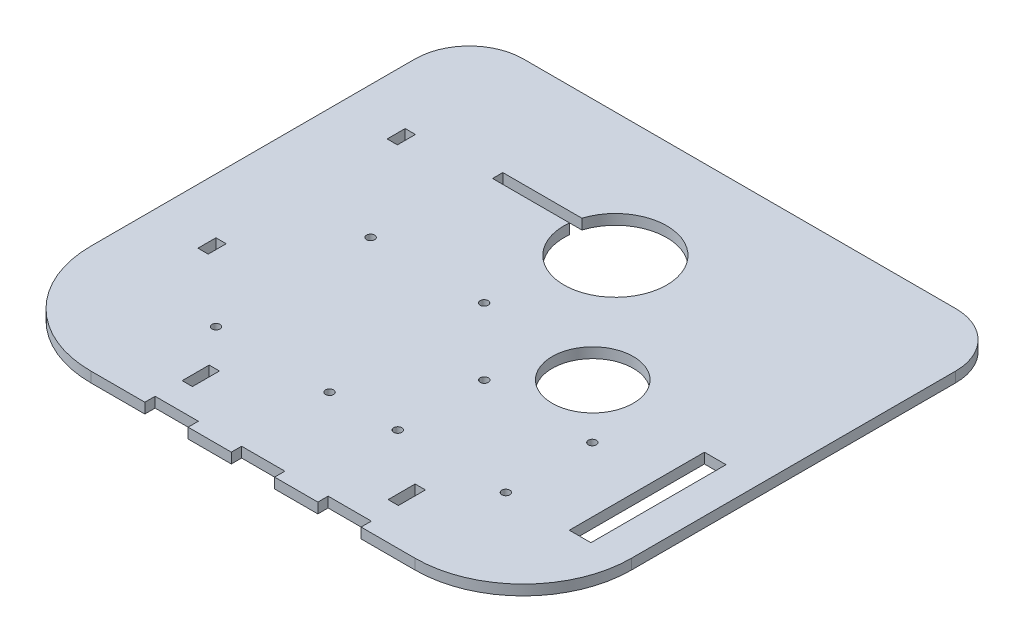
SolidWorks part; units mm, degrees
ref_plane "Front Plane" through (0, 0, 0) normal (0, 0, 1) x (1, 0, 0)
ref_plane "Top Plane" through (0, 0, 0) normal (0, 1, 0) x (1, 0, 0)
ref_plane "Right Plane" through (0, 0, 0) normal (1, 0, 0) x (0, 0, -1)
sketch "Sketch1" plane through (0, 0, 0) normal (0, 1, 0) x (1, 0, 0)
  line L1 (-127, 114.3) -> (127, 114.3)
  line L2 (-127, 114.3) -> (-127, -114.3)
  line L3 (-127, -114.3) -> (127, -114.3)
  line L4 (127, 114.3) -> (127, -114.3)
  line L5 (-127, 114.3) -> (127, -114.3) construction
  line L6 (-127, -114.3) -> (127, 114.3) construction
  point P0 (0, 0)
  dimension "D1" = 254
  dimension "D2" = 228.6
extrude "Boss-Extrude1" add sketch "Sketch1" along normal blind 4.826
sketch "Sketch4" plane through (0, 4.826, 0) normal (0, 1, 0) x (1, 0, 0)
  line L0 (0, -114.3) -> (0, 114.3) construction
  line L1 (-127, -114.3) -> (127, -114.3) construction
  line L2 (127, 114.3) -> (-127, 114.3) construction
  line L3 (-127, 88.9) -> (-101.6, 88.9) construction
  line L4 (-127, 114.3) -> (-127, -114.3) construction
  line L5 (-101.6, 88.9) -> (-101.6, 114.3) construction
  line L6 (-127, 88.9) -> (-127, 114.3)
  line L7 (-127, 114.3) -> (-101.6, 114.3)
  line L8 (127, 88.9) -> (127, 114.3)
  line L9 (127, 114.3) -> (101.6, 114.3)
  arc A0 (-127, 88.9) -> (-101.6, 114.3) centre (-101.6, 88.9) cw
  arc A1 (127, 88.9) -> (101.6, 114.3) centre (101.6, 88.9) ccw
  dimension "D1" = 25.4
  dimension "D2" = 25.4
extrude "Cut-Extrude3" cut sketch "Sketch4" against normal blind 4.826
sketch "Sketch19" plane through (0, 4.826, 0) normal (0, 1, 0) x (1, 0, 0)
  line L0 (-101, -39.1583) -> (-101, -30.6917) construction
  line L1 (-101, -39.1583) -> (-96.174, -39.1583) construction
  line L2 (-96.174, -39.1583) -> (-96.174, -30.6917) construction
  line L3 (-101, -30.6917) -> (-96.174, -30.6917) construction
  line L4 (-101, 49.7417) -> (-101, 58.2083) construction
  line L5 (-101, 49.7417) -> (-96.174, 49.7417) construction
  line L6 (-96.174, 49.7417) -> (-96.174, 58.2083) construction
  line L7 (-101, 58.2083) -> (-96.174, 58.2083) construction
  line L8 (-101, -39.1583) -> (-101, -30.6917)
  line L9 (-101, -39.1583) -> (-96.174, -39.1583)
  line L10 (-96.174, -39.1583) -> (-96.174, -30.6917)
  line L11 (-101, -30.6917) -> (-96.174, -30.6917)
  line L12 (-101, 49.7417) -> (-101, 58.2083)
  line L13 (-101, 49.7417) -> (-96.174, 49.7417)
  line L14 (-96.174, 49.7417) -> (-96.174, 58.2083)
  line L15 (-101, 58.2083) -> (-96.174, 58.2083)
extrude "Cut-Extrude16" cut sketch "Sketch19" against normal through all
fillet "Fillet11" radius 50.8 2 edges at (-127, 2.413, 114.3) (127, 2.413, 114.3)
sketch "Sketch20" plane through (0, 0, 0) normal (0, -1, 0) x (1, 0, 0)
  line L1 (101, 66.675) -> (111.16, 66.675)
  line L2 (101, 66.675) -> (101, 3.175)
  line L3 (101, 3.175) -> (111.16, 3.175)
  line L4 (111.16, 66.675) -> (111.16, 3.175)
  dimension "D1" = 10.16
extrude "Cut-Extrude17" cut sketch "Sketch20" against normal through all
sketch "Sketch23" plane through (0, 4.826, 0) normal (0, 1, 0) x (1, 0, 0)
  circle A0 centre (70.7411, -25.5764) radius 1.905 construction
  circle A1 centre (70.7411, -66.2164) radius 1.905 construction
  circle A2 centre (19.9411, -25.5764) radius 1.905 construction
  circle A3 centre (19.9411, -66.2164) radius 1.905 construction
  circle A4 centre (-11.4804, 5.7926) radius 1.905 construction
  circle A5 centre (-64.8204, 5.7926) radius 1.905 construction
  circle A6 centre (-64.8204, -66.8514) radius 1.905 construction
  circle A7 centre (-11.4804, -66.8514) radius 1.905 construction
  circle A8 centre (70.7411, -25.5764) radius 1.905
  circle A9 centre (70.7411, -66.2164) radius 1.905
  circle A10 centre (19.9411, -25.5764) radius 1.905
  circle A11 centre (19.9411, -66.2164) radius 1.905
  circle A12 centre (-11.4804, 5.7926) radius 1.905
  circle A13 centre (-64.8204, 5.7926) radius 1.905
  circle A14 centre (-64.8204, -66.8514) radius 1.905
  circle A15 centre (-11.4804, -66.8514) radius 1.905
extrude "Cut-Extrude18" cut sketch "Sketch23" against normal through all
sketch "Sketch24" plane through (0, 0, 0) normal (0, -1, 0) x (1, 0, 0)
  line L0 (50.8, 114.3) -> (50.8, 109.474) construction
  line L1 (50.8, 114.3) -> (50.8, 109.474)
  line L2 (50.8, 114.3) -> (50.8, 109.474)
  line L3 (30.48, 114.3) -> (50.8, 114.3) construction
  line L4 (30.48, 109.474) -> (50.8, 109.474) construction
  line L5 (30.48, 114.3) -> (30.48, 109.474) construction
  line L6 (10.16, 114.3) -> (10.16, 109.474) construction
  line L7 (-10.16, 109.474) -> (10.16, 109.474) construction
  line L8 (-10.16, 114.3) -> (-10.16, 109.474) construction
  line L9 (-10.16, 114.3) -> (10.16, 114.3) construction
  line L10 (-30.48, 114.3) -> (-30.48, 109.474) construction
  line L11 (-50.8, 114.3) -> (-30.48, 114.3) construction
  line L12 (-50.8, 114.3) -> (-50.8, 109.474) construction
  line L13 (-50.8, 109.474) -> (-30.48, 109.474) construction
  line L14 (30.48, 114.3) -> (50.8, 114.3)
  line L15 (50.8, 114.3) -> (50.8, 109.474)
  line L16 (30.48, 109.474) -> (50.8, 109.474)
  line L17 (30.48, 114.3) -> (30.48, 109.474)
  line L18 (10.16, 114.3) -> (10.16, 109.474)
  line L19 (-10.16, 109.474) -> (10.16, 109.474)
  line L20 (-10.16, 114.3) -> (-10.16, 109.474)
  line L21 (-10.16, 114.3) -> (10.16, 114.3)
  line L22 (-30.48, 114.3) -> (-30.48, 109.474)
  line L23 (-50.8, 114.3) -> (-30.48, 114.3)
  line L24 (-50.8, 114.3) -> (-50.8, 109.474)
  line L25 (-50.8, 109.474) -> (-30.48, 109.474)
  line M21 (76.2, 114.3) -> (-76.2, 114.3)
extrude "Cut-Extrude19" cut sketch "Sketch24" against normal through all contours L17 L16 L1 M21 | L24 L25 L22 M21 | L21 L18 L19 L20 region at (-40.64, 0, 111.887) region at (40.64, 0, 111.887)
sketch "Sketch26" plane through (0, 0, 0) normal (0, -1, 0) x (1, 0, 0)
  circle A0 centre (0, -55.982) radius 24.13 construction
  circle A1 centre (0, -55.982) radius 24.13
extrude "Cut-Extrude20" cut sketch "Sketch26" against normal through all
sketch "Sketch27" plane through (0, 0, 0) normal (0, -1, 0) x (1, 0, 0)
  line L0 (-45.974, 84.074) -> (-45.974, 96.774) construction
  line L1 (-50.8, 96.774) -> (-45.974, 96.774) construction
  line L2 (-50.8, 84.074) -> (-50.8, 96.774) construction
  line L3 (-50.8, 84.074) -> (-45.974, 84.074) construction
  line L4 (50.8, 84.074) -> (50.8, 96.774) construction
  line L5 (50.8, 84.074) -> (45.974, 84.074) construction
  line L6 (45.974, 84.074) -> (45.974, 96.774) construction
  line L7 (50.8, 96.774) -> (45.974, 96.774) construction
  line L8 (-45.974, 84.074) -> (-45.974, 96.774)
  line L9 (-50.8, 96.774) -> (-45.974, 96.774)
  line L10 (-50.8, 84.074) -> (-50.8, 96.774)
  line L11 (-50.8, 84.074) -> (-45.974, 84.074)
  line L12 (50.8, 84.074) -> (50.8, 96.774)
  line L13 (50.8, 84.074) -> (45.974, 84.074)
  line L14 (45.974, 84.074) -> (45.974, 96.774)
  line L15 (50.8, 96.774) -> (45.974, 96.774)
extrude "Cut-Extrude21" cut sketch "Sketch27" against normal through all
sketch "Sketch28" plane through (0, 4.826, 0) normal (0, 1, 0) x (1, 0, 0)
  line L0 (75.3131, -20.4964) -> (75.3131, -71.2964) construction
  circle A0 centre (45.3411, 0) radius 19.05
  dimension "D1" = 38.1
  dimension "D2" = 29.972
extrude "Cut-Extrude22" cut sketch "Sketch28" against normal through all
sketch "Sketch29" plane through (0, 4.826, 0) normal (0, 1, 0) x (1, 0, 0)
  line L1 (-25.6038, 63.246) -> (-60.1527, 63.246)
  line L2 (-25.6038, 63.246) -> (-25.6038, 58.42)
  line L3 (-25.6038, 58.42) -> (-60.1527, 58.42)
  line L4 (-60.1527, 63.246) -> (-60.1527, 58.42)
  line L5 (-25.6038, 63.246) -> (-20.7196, 63.246)
  line L6 (-25.6038, 63.246) -> (-25.6038, 58.42)
  line L7 (-25.6038, 58.42) -> (-20.7196, 58.42)
  line L8 (-20.7196, 63.246) -> (-20.7196, 58.42)
  circle M11 centre (0, 55.982) radius 24.13
extrude "Cut-Extrude23" cut sketch "Sketch29" against normal through all contours L1 L4 L3 L2 | L2 L7 L5 M11 region at (-42.8782, 4.826, -60.833) region at (-24.5783, 4.826, -61.0319)
equation "\"MDF\"= 0.19in"
equation "\"GenDiameter\"= 60mm"
equation "\"GenCutDiameter\" = 1.8in"
equation "\"GenCutDistance\" = 1"
equation "\"TowerHeight\" = 6in"
equation "\"TowerFrontBase\" = 3in"
equation "\"FunnelHeight\" = 1in"
equation "\"FunnelAngle\" = 20"
equation "\"TowerSideBase\" = 3in"
equation "\"BaseLength\" = 9in"
equation "\"BaseWidth\" = 10in"
equation "\"WheelHoleLength\" = 3.25in"
equation "\"WheelHoleWidth\" = 26mm"
equation "\"DropLength\" = 1in"
equation "\"D1@Sketch1\"=\"BaseWidth\""
equation "\"D2@Sketch1\"=\"BaseLength\""
equation "\"D1@Boss-Extrude1\"=\"MDF\""
equation "\"WheelHoleFromBack\" = 1.5in"
equation "\"DropWidth\" = 8.5in"
equation "\"BumperWidth\" = 2in"
equation "\"D1@Cut-Extrude3\"=\"MDF\""
equation "\"DropWidthTop\" = 0in"
